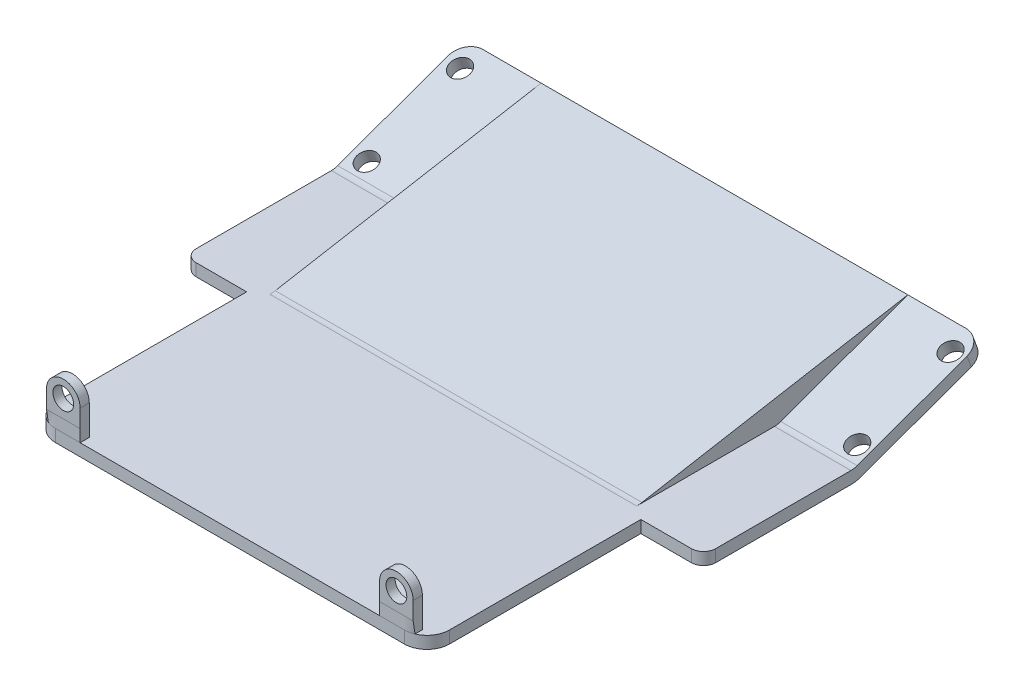
SolidWorks part; units mm, degrees
ref_plane "前视基准面" through (0, 0, 0) normal (0, 0, 1) x (1, 0, 0)
ref_plane "上视基准面" through (0, 0, 0) normal (0, 1, 0) x (1, 0, 0)
ref_plane "右视基准面" through (0, 0, 0) normal (1, 0, 0) x (0, 0, -1)
sketch "草图1" plane through (0, 0, 0) normal (0, 1, 0) x (1, 0, 0)
  line L0 (-15, -259.0169) -> (-15, 12805.6838) construction
  line L1 (15, -261.2731) -> (15, 12803.4276) construction
  line L2 (0, -1000) -> (0, 49000) construction
  line L3 (-1006.7233, 60) -> (48993.2767, 60) construction
  line L4 (-1005.83, 0) -> (48994.17, 0) construction
  line L5 (-1015, 1.7) -> (48985, 1.7) construction
  line L6 (-1015, 58.3) -> (48985, 58.3) construction
  line L7 (-32.25, -984.2827) -> (-32.25, 49015.7173) construction
  line L8 (32.25, -985.1) -> (32.25, 49014.9) construction
  line L9 (-28.55, 62) -> (28.55, 62)
  line L10 (32.25, 58.3) -> (32.25, 1.7)
  line L11 (28.55, -2) -> (-28.55, -2)
  line L12 (-32.25, 1.7) -> (-32.25, 58.3)
  arc A5 (-32.25, 1.7) -> (-28.55, -2) centre (-28.55, 1.7) ccw
  arc A6 (32.25, 1.7) -> (28.55, -2) centre (28.55, 1.7) cw
  arc A7 (28.55, 62) -> (32.25, 58.3) centre (28.55, 58.3) cw
  arc A8 (-28.55, 62) -> (-32.25, 58.3) centre (-28.55, 58.3) ccw
  dimension "D4" = 56.6
  dimension "D8" = 64.5
  dimension "D1" = 30
  dimension "D2" = 15
  dimension "D3" = 60
  dimension "D9" = 32.25
extrude "凸台-拉伸2" add sketch "草图1" against normal blind 2
sketch "草图4" plane through (0, 0, 0) normal (0, 1, 0) x (1, 0, 0)
  line L0 (-25.5, -990.3861) -> (-25.5, 49009.6139) construction
  line L1 (25.5, -991.9534) -> (25.5, 49008.0466) construction
  line L2 (-29, -982.9974) -> (-29, 49017.0026) construction
  line L3 (29, -984.9677) -> (29, 49015.0323) construction
  line L4 (0, -1000) -> (0, 49000) construction
  line L8 (-28.55, -2) -> (28.55, -2) construction
  line L14 (-30, -998.5041) -> (-30, 49001.4959) construction
  line L15 (-24.5, -999.0098) -> (-24.5, 49000.9902) construction
  line L17 (-30, -0.5) -> (-30, -1.704)
  line L18 (-30, -0.5) -> (-24.5, -0.5)
  line L19 (-24.5, -0.5) -> (-24.5, -2)
  line L20 (-28.55, -2) -> (-24.5, -2)
  arc A2 (-28.55, -2) -> (-30, -1.704) centre (-28.55, 1.7) cw
  dimension "D6" = 1
  dimension "D1" = 51
  dimension "D2" = 58
  dimension "D3" = 29
  dimension "D4" = 25.5
  dimension "D7" = 1
ref_plane "基准面4" through (0, 2, 0) normal (0, 1, 0) x (1, 0, 0)
sketch "草图5" plane through (0, 2, 0) normal (0, 1, 0) x (1, 0, 0)
  line L6 (-30, -200998.5041) -> (-30, 249001.4959) construction
  line L7 (-30, -2) -> (-30, -0.5)
  line L8 (-30, -0.5) -> (-24.5, -0.5)
  line L9 (-24.5, -0.5) -> (-24.5, -2)
  line L11 (-24.5, -2) -> (-28.55, -2)
  line L12 (-28.55, -2) -> (-30, -2)
loft "放样4" add profiles "草图4", "草图5" connector at (-24.5, 0, 2) connector at (-24.5, 2, 2)
sketch "草图6" plane through (0, 0, 0) normal (0, 0, 1) x (1, 0, 0)
  line L0 (-1028.1213, 3.2) -> (48971.8787, 3.2) construction
  line L1 (-24.5, 0) -> (28.55, 0) construction
  line L2 (-1026.7035, 6.6) -> (48973.2965, 6.6) construction
  line L3 (-24.5, 4.9) -> (-24.5, 2)
  line L4 (-24.5, 2) -> (-24.5, 0) construction
  line L5 (-30, 2) -> (-30, 4.9)
  line L6 (35.475, 2) -> (-35.475, 2) construction
  line L7 (-30, 0) -> (-30, 2) construction
  line L8 (-30, 2) -> (-24.5, 2)
  circle A0 centre (-27.25, 4.9) radius 1.7
  arc A1 (-24.5, 4.9) -> (-30, 4.9) centre (-27.25, 4.9) ccw
  dimension "D3" = 2.75
  dimension "D1" = 3.2
  dimension "D2" = 3.4
extrude "凸台-拉伸3" add sketch "草图6" along normal blind 1.5 from offset 0.5
mirror "镜向1" about plane through (0, 0, 0) normal (1, 0, 0) of "放样4", "凸台-拉伸3"
sketch "草图7" plane through (0, 0, 0) normal (0, 1, 0) x (1, 0, 0)
  line L0 (-42.5, 58) -> (42.5, 58)
  line L1 (42.5, 58) -> (42.5, 33)
  line L2 (42.5, 33) -> (-42.5, 33)
  line L3 (-42.5, 33) -> (-42.5, 58)
  line L4 (28.55, 62) -> (-28.55, 62) construction
  line L5 (0, 62) -> (0, 58) construction
  dimension "D1" = 85
  dimension "D2" = 42.5
  dimension "D3" = 4
  dimension "D4" = 25
extrude "凸台-拉伸4" add sketch "草图7" against normal blind 2
fillet "圆角2" radius 10 1 edges at (-32.25, -1, -58)
fillet "圆角4" radius 10 1 edges at (32.25, -1, -58)
sketch "草图9" plane through (0, 0, 0) normal (0, 1, 0) x (1, 0, 0)
  line L0 (-38.2247, 58) -> (-42.5, 58) construction
  line L1 (-51.2589, 67.4647) -> (50.0267, 67.4647)
  line L2 (-51.2589, 67.4647) -> (-51.2589, 58)
  line L3 (-51.2589, 58) -> (50.0267, 58)
  line L4 (50.0267, 67.4647) -> (50.0267, 58)
extrude "切除-拉伸2" cut sketch "草图9" against normal blind 2
fillet "圆角8" radius 2 1 edges at (-42.5, -1, -33)
fillet "圆角9" radius 2 1 edges at (42.5, -1, -33)
sketch "草图10" plane through (42.5, 0, 0) normal (1, 0, 0) x (0, 0, -1)
  line L0 (58, -2) -> (79.6129, 5.8665)
  line L1 (35, -2) -> (58, -2) construction
  line L3 (78.9289, 7.7458) -> (57.316, -0.1206)
  line L5 (78.9289, 7.7458) -> (79.6129, 5.8665)
  line L6 (58, -2) -> (57.316, -0.1206)
  line L7 (58, -2) -> (40.1911, -8.4819) construction
  dimension "D1" = 160
  dimension "D2" = 2
  dimension "D3" = 90
  dimension "D4" = 2
  dimension "D5" = 90
  dimension "D6" = 23
  dimension "D7" = 20
extrude "凸台-拉伸5" add sketch "草图10" against normal up to surface (85 mm away) up to face at (-42.5, -1, -46.5)
fillet "圆角10" radius 5 1 edges at (0, -2, -58)
sketch "草图13" plane through (0, -18.5275, -6.7435) normal (0, 0.9397, 0.342) x (1, 0, 0)
  line L0 (-39.936, 73.2791) -> (40.314, 73.2791) construction
  line L1 (0, 73.2791) -> (0, 0) construction
  line L2 (-39.936, 73.2791) -> (-39.936, 57.0291) construction
  line L3 (-39.936, 57.0291) -> (40.314, 57.0291) construction
  line L4 (40.314, 57.0291) -> (40.314, 73.2791) construction
  circle A0 centre (-39.936, 73.2791) radius 1.625
  circle A1 centre (40.314, 73.2791) radius 1.625
  circle A2 centre (40.314, 57.0291) radius 1.625
  circle A3 centre (-39.936, 57.0291) radius 1.625
  dimension "D3" = 3.25
  dimension "D4" = 3.25
  dimension "D5" = 3.25
  dimension "D6" = 3.25
  dimension "D1" = 80.25
  dimension "D2" = 16.25
extrude "切除-拉伸3" cut sketch "草图13" against normal blind 10
ref_plane "基准面5" through (0, 0, 0) normal (-1, 0, 0) x (0, 0, 1)
sketch "草图14" plane through (0, 0, 0) normal (-1, 0, 0) x (0, 0, 1)
  line L5 (-78.9289, 7.7458) -> (-57.6473, 0)
  line L6 (-57.6473, 0) -> (-35, 0)
  line L7 (-35, 0) -> (-78.9289, 7.7458)
  point P2 (0, 0)
  point P4 (0, 0)
extrude "凸台-拉伸6" add sketch "草图14" along normal mid plane 60
fillet "圆角12" radius 5 1 edges at (0, 0, -35)
fillet "圆角13" radius 3 2 edges at (-42.5, 6.8062, -79.2709) (42.5, 6.8062, -79.2709)
fillet "圆角15" radius 3 2 edges at (36.25, 0, -57.6473) (-36.25, 0, -57.6473)
